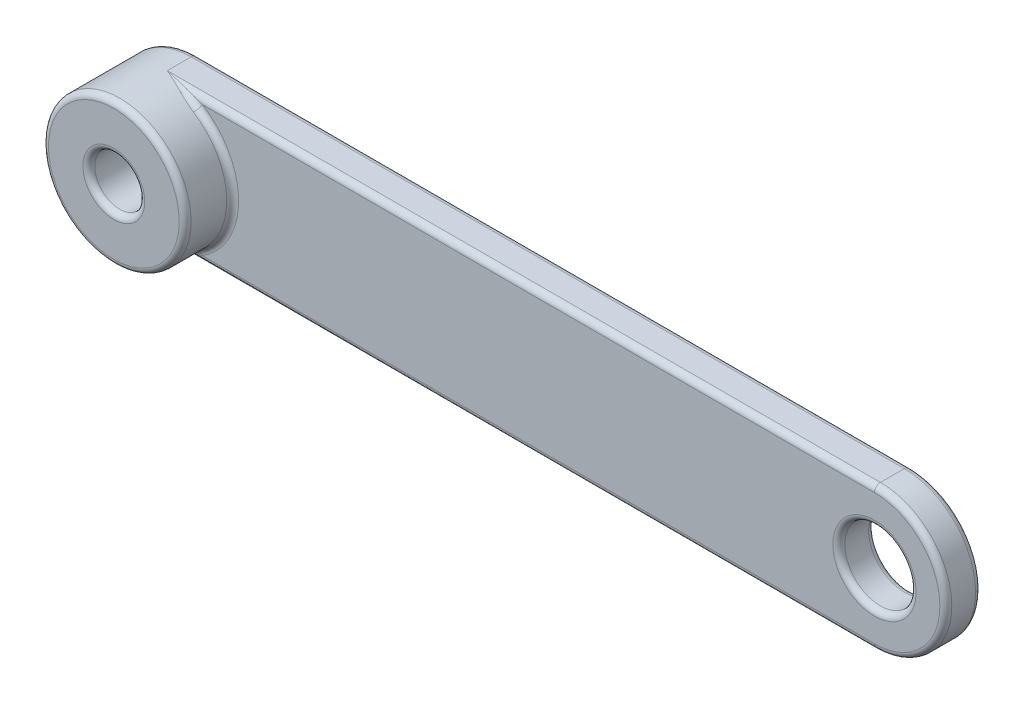
SolidWorks part; units mm, degrees
ref_plane "Front Plane" through (0, 0, 0) normal (0, 0, 1) x (1, 0, 0)
ref_plane "Top Plane" through (0, 0, 0) normal (0, 1, 0) x (1, 0, 0)
ref_plane "Right Plane" through (0, 0, 0) normal (1, 0, 0) x (0, 0, -1)
ref_plane "Plane1" through (0, 0, 0) normal (0, 0, -1) x (-1, 0, 0)
sketch "Sketch1" plane through (0, 0, 0) normal (0, 0, -1) x (-1, 0, 0)
  line L0 (30, 6) -> (-30, 6)
  line L1 (-30, -6) -> (30, -6)
  arc A0 (30, -6) -> (30, 6) centre (30, 0) ccw
  arc A1 (-30, 6) -> (-30, -6) centre (-30, 0) ccw
  point P6 (0, 6)
  dimension "D1" = 60
  dimension "D2" = 12
extrude "Boss-Extrude1" add sketch "Sketch1" against normal mid plane 3
hole_wizard "Ø6.0mm Dowel Hole1" positions "Sketch3" profile "Sketch2" hole size "Ø6.0" standard "ISO" end condition through all
sketch "Sketch3" plane through (0, 0, -1.5) normal (0, 0, -1) x (-1, 0, 0)
  arc A0 (-30, 6) -> (-30, -6) centre (-30, 0) ccw construction
  point P1 (-30, 0)
sketch "Sketch2" plane through (30, 0, -1.5) normal (1, 0, 0) x (0, 1, 0)
  line L0 (0, 0) -> (0, 3)
  line L1 (0, 3) -> (3, 3)
  line L2 (3, 3) -> (3, 0)
  line L5 (3, 0) -> (0, 0)
  line L11 (0, -6.35) -> (0, 107.95) construction
  dimension "Thru Hole Dia." = 6
  dimension "Thru Hole Depth" = 3
sketch "Sketch6" plane through (0, 0, 1.5) normal (0, 0, -1) x (-1, 0, 0)
  circle A0 centre (30, 0) radius 6
extrude "Boss-Extrude2" add sketch "Sketch6" against normal blind 4
fillet "Fillet1" radius 0.5 11 edges at (27, 0, 1.5) (-24, 0, 1.5) (0, -6, 1.5) (0, 6, 1.5) (36, 0, 1.5) (27, 0, -1.5) (36, 0, -1.5) (0, -6, -1.5) (0, 6, -1.5) (-36, 0, -1.5) (-36, 0, 5.5)
hole_wizard "M5 Tapped Hole1" positions "Sketch4" profile "Sketch5" tap size "M5" standard "ISO" end condition through all
sketch "Sketch4" plane through (0, 0, -1.5) normal (0, 0, -1) x (-1, 0, 0)
  point P0 (30, 0)
sketch "Sketch5" plane through (-30, 0, -1.5) normal (1, 0, 0) x (0, 1, 0)
  line L0 (0, 0) -> (0, 7)
  line L1 (0, 7) -> (2.1, 7)
  line L2 (2.1, 7) -> (2.1, 0)
  line L5 (2.1, 0) -> (0, 0)
  line L11 (0, -6.35) -> (0, 107.95) construction
  dimension "Thru Tap Drill Dia." = 4.2
  dimension "Thru Tap Drill Depth" = 7
cosmetic thread "Hole Thread2" parameters "D2"=5
fillet "Fillet2" radius 0.5 2 edges at (-32.1, 0, -1.5) (-32.1, 0, 5.5)
